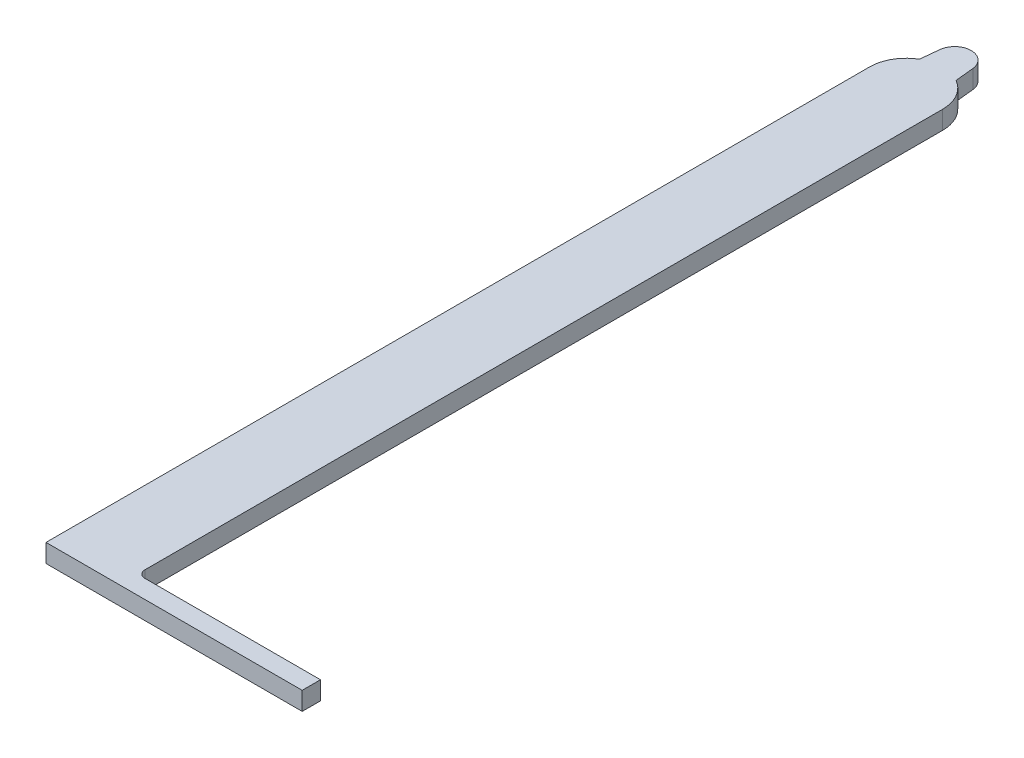
SolidWorks part; units mm, degrees
ref_plane "Front Plane" through (0, 0, 0) normal (0, 0, 1) x (1, 0, 0)
ref_plane "Top Plane" through (0, 0, 0) normal (0, 1, 0) x (1, 0, 0)
ref_plane "Right Plane" through (0, 0, 0) normal (1, 0, 0) x (0, 0, -1)
sketch "Sketch1" plane through (0, 0, 0) normal (0, 1, 0) x (1, 0, 0)
  line L1 (-12.7, 0) -> (12.7, 0)
  line L2 (-12.7, 0) -> (-12.7, -279.4)
  line L3 (-12.7, -279.4) -> (12.7, -279.4)
  line L4 (12.7, 0) -> (12.7, -279.4)
  circle A0 centre (0, 0) radius 12.7
  dimension "D1" = 25.4
  dimension "D2" = 279.4
extrude "Boss-Extrude1" add sketch "Sketch1" along normal blind 6.35 contours A0 L2 L3 L4 | L1 A0 | L1 A0 region at (0, 0, -5.39) region at (0, 0, 144.6724) region at (0, 0, 5.39)
sketch "Sketch2" plane through (0, 6.35, 0) normal (0, 1, 0) x (1, 0, 0)
  line L1 (-12.7, -279.4) -> (76.2, -279.4)
  line L2 (-12.7, -279.4) -> (-12.7, -285.75)
  line L3 (-12.7, -285.75) -> (76.2, -285.75)
  line L4 (76.2, -279.4) -> (76.2, -285.75)
  dimension "D1" = 88.9
  dimension "D2" = 6.35
extrude "Boss-Extrude2" add sketch "Sketch2" against normal up to surface (6.35 mm away) up to face at (0, 0, 136.525)
fillet "Fillet1" radius 2.54 1 edges
sketch "Sketch3" plane through (0, 0, 0) normal (0, -1, 0) x (-1, 0, 0)
  line L4 (-7.3841, 1.2138) -> (7.3841, 1.2138)
  line L6 (-7.3841, 1.2138) -> (-5.6981, 17.4684)
  line L7 (5.6981, 17.4684) -> (7.3841, 1.2138)
  line L8 (-7.3841, 1.2138) -> (-5.6981, 17.4684)
  line L9 (5.6981, 17.4684) -> (7.3841, 1.2138)
  arc A3 (5.6981, 17.4684) -> (-5.6981, 17.4684) centre (0, 16.8774) ccw
  arc A4 (5.6981, 17.4684) -> (-5.6981, 17.4684) centre (0, 16.8774) ccw
  dimension "D1" = 3.175
extrude "Boss-Extrude3" add sketch "Sketch3" against normal up to surface (6.35 mm away) up to face at (28.2277, 6.35, 179.508)
